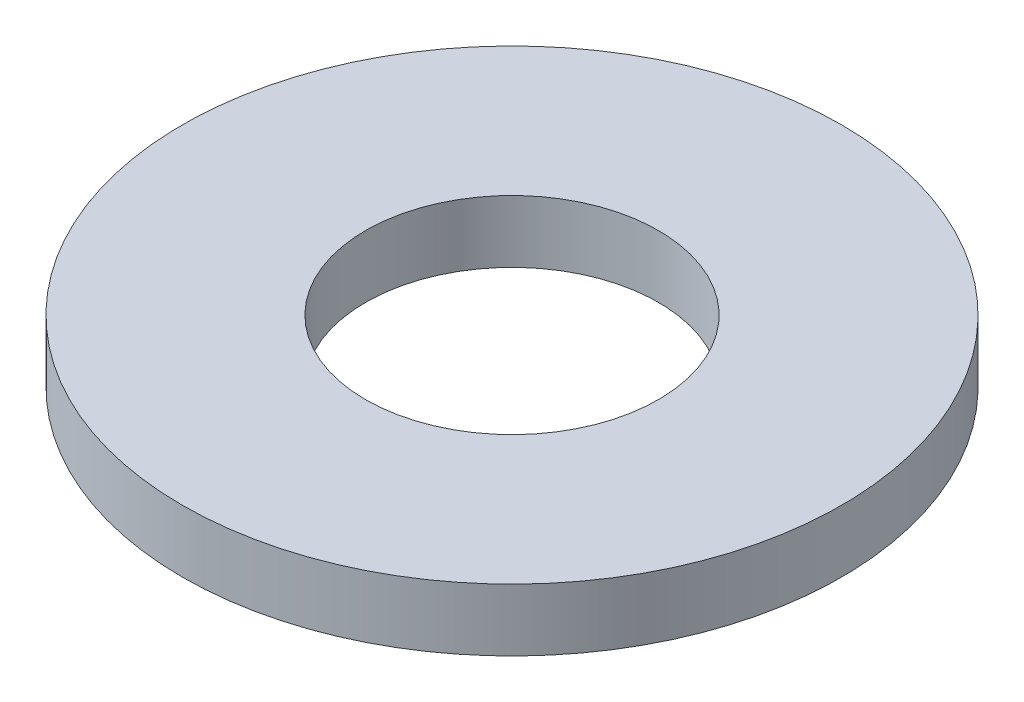
SolidWorks part; units mm, degrees
ref_plane "Front Plane" through (0, 0, 0) normal (0, 0, 1) x (1, 0, 0)
ref_plane "Top Plane" through (0, 0, 0) normal (0, 1, 0) x (1, 0, 0)
ref_plane "Right Plane" through (0, 0, 0) normal (1, 0, 0) x (0, 0, -1)
sketch "Sketch1" plane through (0, 0, 0) normal (0, 1, 0) x (1, 0, 0)
  circle A0 centre (0, 0) radius 90
  dimension "FLANGE_OD" = 180
extrude "Boss-Extrude1" add sketch "Sketch1" along normal blind 17
sketch "Sketch2" plane through (0, 0, 0) normal (0, 1, 0) x (1, 0, 0)
  circle A0 centre (0, 0) radius 40
  dimension "BORE_D" = 80
extrude "Cut-Extrude1" cut sketch "Sketch2" along normal through all
sketch "Sketch3" plane through (0, 17, 0) normal (0, 1, 0) x (1, 0, 0)
  circle A0 centre (0, 0) radius 24.9307 construction
  circle A1 centre (-24.9307, 0) radius 8.6481
  dimension "BOLT_D" = 17.2963
  dimension "BOLT_PCD" = 49.8614
extrude "Cut-Extrude2" cut sketch "Sketch3" against normal blind 12.375 rebuild error yes
pattern_circular "CirPattern1" count 4 over 360 rebuild error yes
